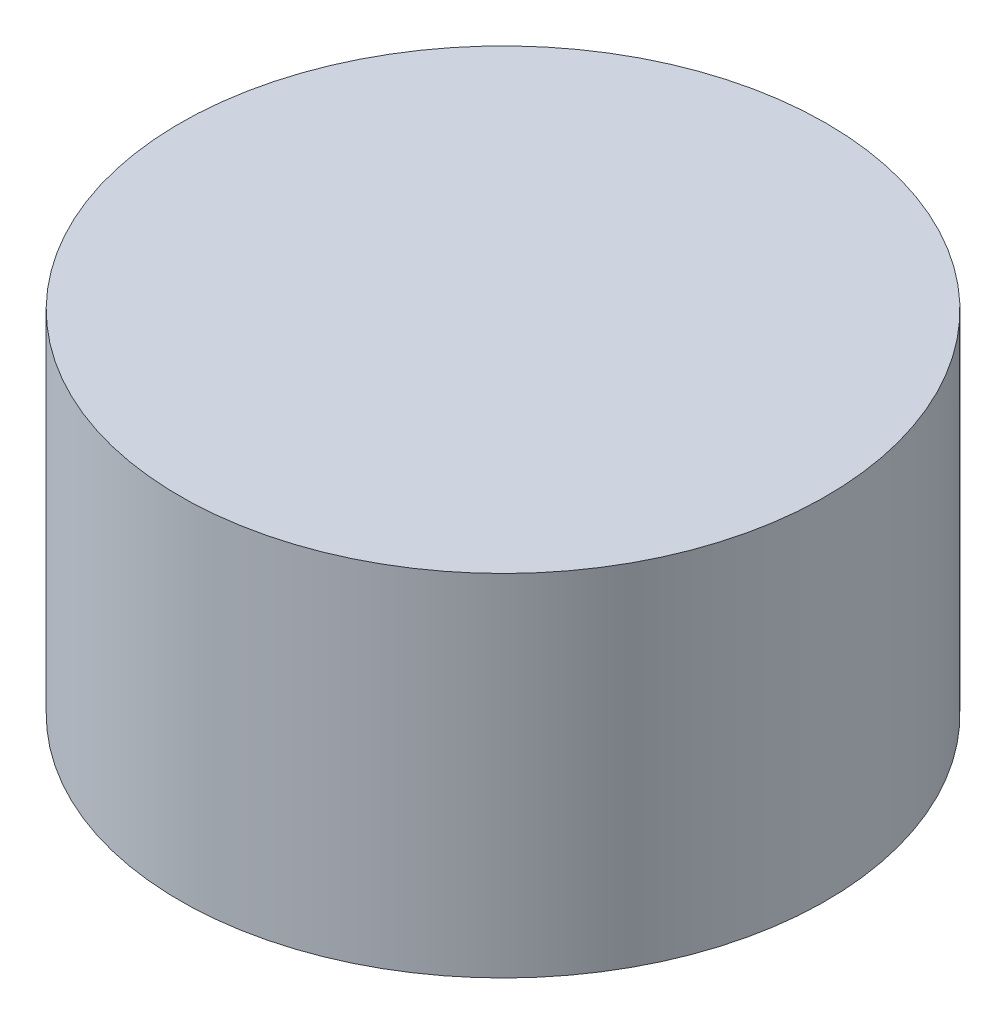
SolidWorks part; units mm, degrees
ref_plane "前基準面" through (0, 0, 0) normal (0, 0, 1) x (1, 0, 0)
ref_plane "上基準面" through (0, 0, 0) normal (0, 1, 0) x (1, 0, 0)
ref_plane "右基準面" through (0, 0, 0) normal (1, 0, 0) x (0, 0, -1)
sketch "草圖1" plane through (0, 0, 0) normal (0, 1, 0) x (1, 0, 0)
  circle A0 centre (0, 0) radius 41.5
  dimension "D1" = 83
extrude "填料-伸長1" add sketch "草圖1" along normal blind 45
